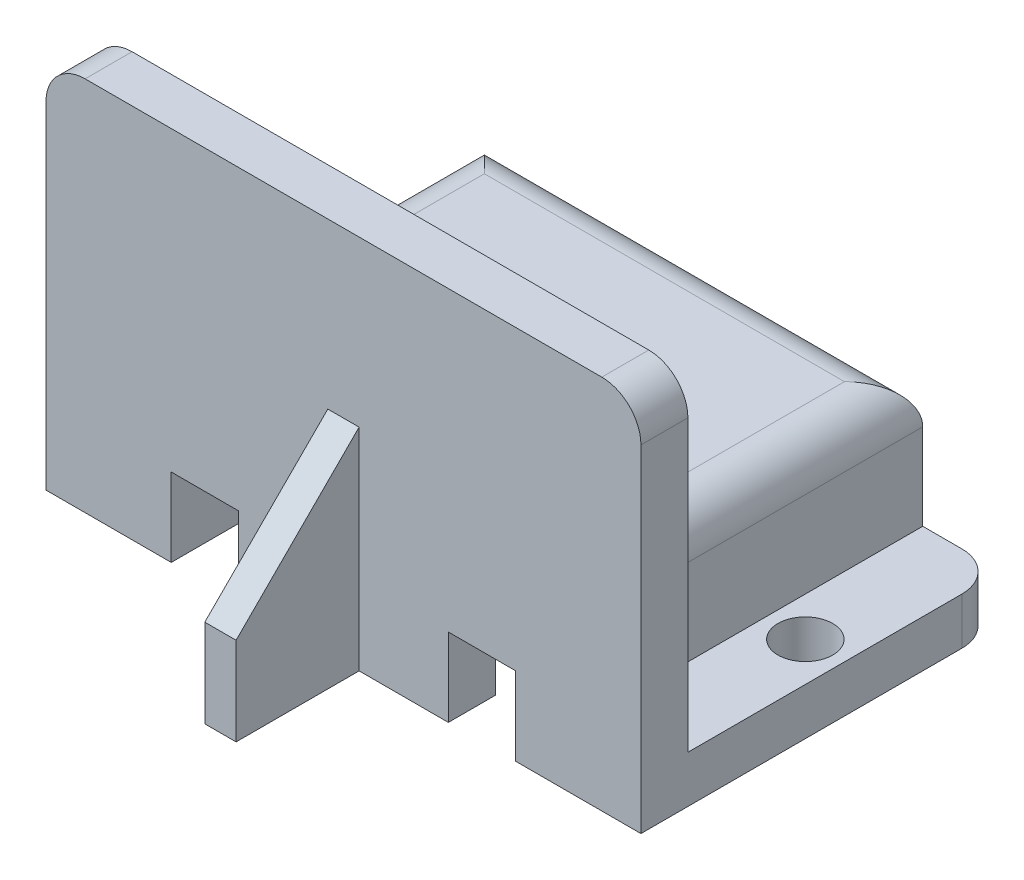
SolidWorks part; units mm, degrees
ref_plane "Front Plane" through (0, 0, 0) normal (0, 0, 1) x (1, 0, 0)
ref_plane "Top Plane" through (0, 0, 0) normal (0, 1, 0) x (1, 0, 0)
ref_plane "Right Plane" through (0, 0, 0) normal (1, 0, 0) x (0, 0, -1)
sketch "Sketch1" plane through (0, 0, 0) normal (1, 0, 0) x (0, 0, -1)
  line L1 (0, 0) -> (3, 0)
  line L2 (0, 0) -> (0, 24)
  line L3 (0, 24) -> (3, 24)
  line L4 (3, 0) -> (3, 24)
  dimension "D1" = 3
  dimension "D2" = 24
extrude "Boss-Extrude1" add sketch "Sketch1" along normal blind 38
sketch "Sketch2" plane through (0, 0, 0) normal (0, 0, 1) x (1, 0, 0)
  line L0 (38, 0) -> (0, 0) construction
  line L1 (18, 0) -> (20, 0)
  line L2 (18, 0) -> (18, 13.4839)
  line L3 (18, 13.4839) -> (20, 13.4839)
  line L4 (20, 0) -> (20, 13.4839)
  line L5 (38, 24) -> (0, 24) construction
  point P6 (19, 24)
  point P7 (19, 13.4839)
  dimension "D1" = 2
extrude "Boss-Extrude2" add sketch "Sketch2" along normal blind 20
chamfer "Chamfer1" distance 20 angle 45 1 edges at (19, 13.4839, 20)
sketch "Sketch3" plane through (0, 0, -3) normal (0, 0, -1) x (-1, 0, 0)
  line L0 (0, 0) -> (0, 24) construction
  line L1 (-38, 3) -> (0, 3)
  line L2 (-38, 3) -> (-38, 0)
  line L3 (-38, 0) -> (0, 0)
  line L4 (0, 3) -> (0, 0)
  line L5 (-38, 0) -> (0, 0) construction
  dimension "D1" = 3
extrude "Boss-Extrude3" add sketch "Sketch3" along normal blind 20
sketch "Sketch4" plane through (0, 0, 0) normal (0, -1, 0) x (1, 0, 0)
  line L0 (38, -23) -> (0, -23) construction
  line L1 (0, -23) -> (0, 0) construction
  line L2 (38, -23) -> (38, 0) construction
  circle A0 centre (2.5, -13) radius 1.75
  circle A1 centre (35.5, -13) radius 1.75
  dimension "D1" = 3.5
  dimension "D2" = 10
  dimension "D3" = 2.5
  dimension "D4" = 2.5
extrude "Cut-Extrude1" cut sketch "Sketch4" against normal through all
sketch "Sketch5" plane through (0, 3, 0) normal (0, 1, 0) x (1, 0, 0)
  line L0 (0, 23) -> (38, 23) construction
  line L1 (5, 23) -> (33, 23)
  line L2 (5, 23) -> (5, 3)
  line L3 (5, 3) -> (33, 3)
  line L4 (33, 23) -> (33, 3)
  line L5 (38, 3) -> (0, 3) construction
  circle A0 centre (2.5, 13) radius 1.75 construction
  circle A1 centre (35.5, 13) radius 1.75 construction
  dimension "D1" = 2.5
  dimension "D2" = 2.5
extrude "Boss-Extrude4" add sketch "Sketch5" along normal blind 8
sketch "Sketch6" plane through (0, 0, 0) normal (0, -1, 0) x (1, 0, 0)
  line L0 (11, -23) -> (27, -23)
  line L2 (27, -23) -> (27, -20)
  line L3 (27, -20) -> (30, -20)
  line L4 (30, -20) -> (30, -3)
  line L5 (30, -3) -> (8, -3)
  line L6 (8, -3) -> (8, -20)
  line L7 (8, -20) -> (11, -20)
  line L8 (11, -20) -> (11, -23)
  line L9 (20, 0) -> (18, 0) construction
  line L10 (33, -3) -> (33, -23) construction
  line L11 (5, -23) -> (5, -3) construction
  line L12 (0, -3) -> (5, -3) construction
  line L14 (38, -23) -> (0, -23) construction
  point P8 (19, 0)
  point P11 (19, -23)
  dimension "D1" = 16
  dimension "D2" = 3
  dimension "D3" = 3
  dimension "D4" = 3
extrude "Cut-Extrude2" cut sketch "Sketch6" against normal offset from surface (8 mm away) 3 up to face at (19, 11, -13)
sketch "Sketch7" plane through (0, 0, -3) normal (0, 0, -1) x (-1, 0, 0)
  line L0 (-30, 0) -> (-8, 0) construction
  line L1 (-30, 0) -> (-25.7004, 0)
  line L2 (-30, 0) -> (-30, 5.0023)
  line L3 (-30, 5.0023) -> (-25.7004, 5.0023)
  line L4 (-25.7004, 0) -> (-25.7004, 5.0023)
  line L5 (-30, 8) -> (-30, 0) construction
  line L6 (-12.2996, 0) -> (-8, 0)
  line L7 (-12.2996, 0) -> (-12.2996, 5.0023)
  line L8 (-12.2996, 5.0023) -> (-8, 5.0023)
  line L9 (-8, 0) -> (-8, 5.0023)
  line L10 (-8, 8) -> (-8, 0) construction
extrude "Cut-Extrude3" cut sketch "Sketch7" against normal blind 15
sketch "Sketch8" plane through (18, 0, 0) normal (-1, 0, 0) x (0, 0, 1)
  line L0 (7.8583, 5.6256) -> (7.8583, 0)
  line L1 (13.4839, 0) -> (0, 13.4839) construction
  line L2 (13.4839, 0) -> (0, 0) construction
  line L3 (7.8583, 0) -> (13.4839, 0)
  line L4 (13.4839, 0) -> (7.8583, 5.6256)
extrude "Cut-Extrude4" cut sketch "Sketch8" against normal blind 15
fillet "Fillet3" radius 2.5 8 edges at (33, 7, -3) (5, 7, -3) (19, 11, -23) (33, 11, -13) (19, 11, -3) (5, 11, -13) (0, 1.5, -23) (38, 1.5, -23)
sketch "Sketch9" plane through (0, 11, 0) normal (0, 1, 0) x (1, 0, 0)
  line L0 (38, 3) -> (0, 3) construction
  line L1 (11, 3) -> (14, 3)
  line L2 (11, 3) -> (11, 13)
  line L3 (11, 13) -> (14, 13)
  line L4 (14, 3) -> (14, 13)
  line L5 (7.5, 20.5) -> (7.5, 5.5) construction
  line L6 (27, 3) -> (24, 3)
  line L7 (27, 3) -> (27, 13)
  line L8 (27, 13) -> (24, 13)
  line L9 (24, 3) -> (24, 13)
  line L10 (30.5, 5.5) -> (30.5, 20.5) construction
  dimension "D1" = 3
  dimension "D2" = 3.5
  dimension "D3" = 3.5
  dimension "D4" = 10
extrude "Boss-Extrude5" add sketch "Sketch9" along normal blind 7.5
chamfer "Chamfer2" distance 7.5 angle 45 2 edges at (12.5, 18.5, -13) (25.5, 18.5, -13)
fillet "Fillet4" radius 2.5 2 edges at (38, 24, -1.5) (0, 24, -1.5)
